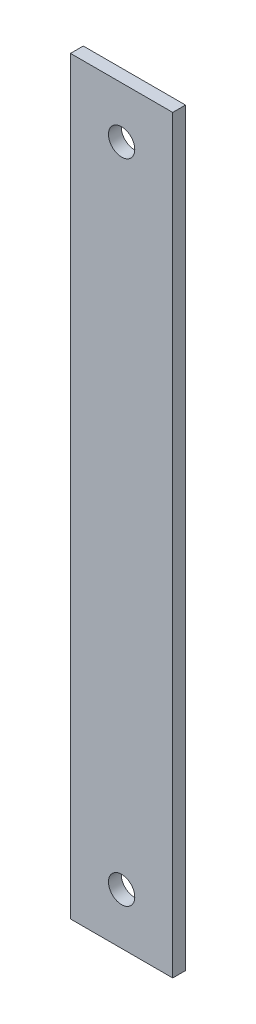
SolidWorks part; units mm, degrees
material "6061-T6 (SS)"
ref_plane "Front Plane" through (0, 0, 0) normal (0, 0, 1) x (1, 0, 0)
ref_plane "Top Plane" through (0, 0, 0) normal (0, 1, 0) x (1, 0, 0)
ref_plane "Right Plane" through (0, 0, 0) normal (1, 0, 0) x (0, 0, -1)
sketch "Sketch1" plane through (0, 0, 0) normal (0, 0, 1) x (1, 0, 0)
  line L1 (0, 0) -> (38.1, 0)
  line L2 (0, 0) -> (0, 279.4)
  line L3 (0, 279.4) -> (38.1, 279.4)
  line L4 (38.1, 0) -> (38.1, 279.4)
  dimension "D1" = 38.1
  dimension "D2" = 279.4
extrude "Boss-Extrude1" add sketch "Sketch1" along normal blind 4.7625
hole_wizard "W (0.386) Diameter Hole1" positions "Sketch3" profile "Sketch2" hole size "W" standard "ANSI Inch" end condition through all
sketch "Sketch3" plane through (0, 0, 4.7625) normal (0, 0, 1) x (1, 0, 0)
  line L0 (19.05, 0) -> (19.05, 19.05) construction
  line L1 (0, 0) -> (38.1, 0) construction
  line L2 (19.05, 19.05) -> (19.05, 260.35) construction
  line L3 (19.05, 260.35) -> (19.05, 279.4) construction
  line L4 (38.1, 279.4) -> (0, 279.4) construction
  point P0 (19.05, 260.35)
  point P2 (19.05, 19.05)
  dimension "D1" = 19.05
sketch "Sketch2" plane through (19.05, 260.35, 4.7625) normal (1, 0, 0) x (0, -1, 0)
  line L0 (0, 0) -> (0, 4.7625)
  line L1 (0, 4.7625) -> (4.9022, 4.7625)
  line L2 (4.9022, 4.7625) -> (4.9022, 0)
  line L5 (4.9022, 0) -> (0, 0)
  line L11 (0, -6.35) -> (0, 107.95) construction
  dimension "Thru Hole Dia." = 9.8044
  dimension "Thru Hole Depth" = 4.7625
